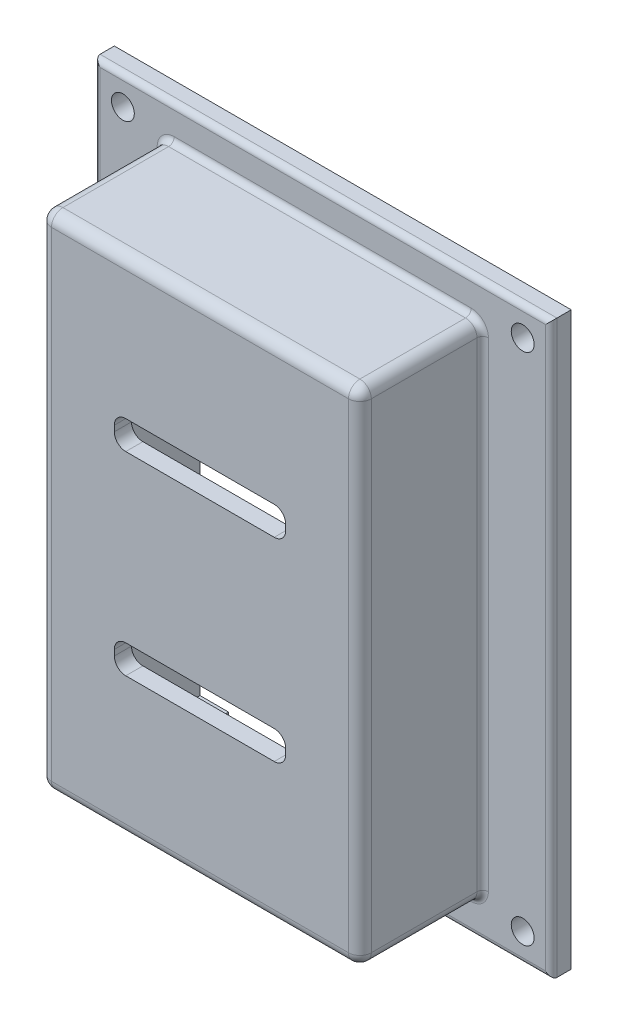
SolidWorks part; units mm, degrees
ref_plane "Front Plane" through (0, 0, 0) normal (0, 0, 1) x (1, 0, 0)
ref_plane "Top Plane" through (0, 0, 0) normal (0, 1, 0) x (1, 0, 0)
ref_plane "Right Plane" through (0, 0, 0) normal (1, 0, 0) x (0, 0, -1)
sketch "Sketch1" plane through (0, 0, 0) normal (0, 0, 1) x (1, 0, 0)
  line L1 (-40, 50) -> (40, 50)
  line L2 (-40, 50) -> (-40, -50)
  line L3 (-40, -50) -> (40, -50)
  line L4 (40, 50) -> (40, -50)
  line L5 (-40, 50) -> (40, -50) construction
  line L6 (-40, -50) -> (40, 50) construction
  point P0 (0, 0)
  dimension "D1" = 100
  dimension "D2" = 80
extrude "Boss-Extrude1" add sketch "Sketch1" along normal blind 3.5
sketch "Sketch3" plane through (0, 0, 3.5) normal (0, 0, 1) x (1, 0, 0)
  line L1 (-28, 44) -> (28, 44)
  line L2 (-28, 44) -> (-28, -44)
  line L3 (-28, -44) -> (28, -44)
  line L4 (28, 44) -> (28, -44)
  line L5 (-28, 44) -> (28, -44) construction
  line L6 (-28, -44) -> (28, 44) construction
  point P0 (0, 0)
  dimension "D1" = 56
  dimension "D2" = 88
extrude "Boss-Extrude2" add sketch "Sketch3" along normal blind 21.5
sketch "Sketch4" plane through (0, 0, 0) normal (0, 0, -1) x (-1, 0, 0)
  line L1 (-25, 41) -> (25, 41)
  line L2 (-25, 41) -> (-25, -41)
  line L3 (-25, -41) -> (25, -41)
  line L4 (25, 41) -> (25, -41)
  line L5 (-25, 41) -> (25, -41) construction
  line L6 (-25, -41) -> (25, 41) construction
  point P0 (0, 0)
  dimension "D1" = 50
  dimension "D2" = 82
extrude "Cut-Extrude4" cut sketch "Sketch4" against normal blind 16
sketch "Sketch7" plane through (0, 0, 16) normal (0, 0, -1) x (-1, 0, 0)
  line L0 (-18, 41) -> (18, 41)
  line L1 (25, 41) -> (-25, 41) construction
  line L2 (25, 41) -> (-25, 41) construction
  line L3 (18, 41) -> (18, 34)
  line L4 (18, 34) -> (25, 34)
  line L5 (25, -41) -> (25, 41) construction
  line L6 (25, 34) -> (25, -34)
  line L7 (25, -34) -> (18, -34)
  line L8 (18, -34) -> (18, -41)
  line L9 (-25, -41) -> (25, -41) construction
  line L10 (18, -41) -> (-18, -41)
  line L11 (-18, -41) -> (-18, -34)
  line L12 (-18, -34) -> (-25, -34)
  line L13 (-25, 41) -> (-25, -41) construction
  line L14 (-25, -34) -> (-25, 34)
  line L15 (-25, 34) -> (-18, 34)
  line L16 (-18, 34) -> (-18, 41)
  dimension "D1" = 68
  dimension "D2" = 7
  dimension "D3" = 36
  dimension "D4" = 7
  dimension "D5" = 68
  dimension "D6" = 36
  dimension "D7" = 7
  dimension "D8" = 7
extrude "Cut-Extrude5" cut sketch "Sketch7" against normal blind 6
sketch "Sketch8" plane through (0, 0, 25) normal (0, 0, 1) x (1, 0, 0)
  line L1 (-15, -19.5) -> (15, -19.5)
  line L2 (-15, -19.5) -> (-15, -14.5)
  line L3 (-15, -14.5) -> (15, -14.5)
  line L4 (15, -19.5) -> (15, -14.5)
  line L5 (-15, -19.5) -> (15, -14.5) construction
  line L6 (-15, -14.5) -> (15, -19.5) construction
  point P0 (0, -17)
  point P5 (0, 0)
  dimension "D1" = 5
  dimension "D2" = 17
  dimension "D3" = 30
extrude "Cut-Extrude6" cut sketch "Sketch8" against normal blind 6
mirror "Mirror1" about plane through (0, 0, 0) normal (0, 1, 0) of "Cut-Extrude6"
sketch "Sketch9" plane through (0, -50, 0) normal (0, -1, 0) x (1, 0, 0)
  line L0 (-40, 0) -> (40, 0) construction
  line L1 (-20, 0) -> (20, 0)
  line L2 (-20, 0) -> (-20, 12)
  line L3 (-20, 12) -> (20, 12)
  line L4 (20, 0) -> (20, 12)
  line L5 (-40, 3.5) -> (-40, 0) construction
  dimension "D1" = 20
  dimension "D2" = 40
  dimension "D3" = 12
extrude "Cut-Extrude7" cut sketch "Sketch9" against normal up to next
sketch "Sketch10" plane through (0, 0, 0) normal (0, 0, -1) x (-1, 0, 0)
  line L1 (-35, 45) -> (35, 45)
  line L2 (-35, 45) -> (-35, -45)
  line L3 (-35, -45) -> (35, -45)
  line L4 (35, 45) -> (35, -45)
  line L5 (-35, 45) -> (35, -45) construction
  line L6 (-35, -45) -> (35, 45) construction
  point P0 (0, 0)
  dimension "D1" = 90
  dimension "D2" = 70
hole_wizard "Ø4.0mm Dowel Hole1" positions "Sketch11" profile "Sketch12" hole size "Ø4.0" standard "ANSI Metric" end condition through all
sketch "Sketch11" plane through (0, 0, 0) normal (0, 0, -1) x (-1, 0, 0)
  point P0 (-35, 45)
  point P3 (35, 45)
  point P6 (35, -45)
  point P9 (-35, -45)
sketch "Sketch12" plane through (35, 45, 0) normal (1, 0, 0) x (0, 1, 0)
  line L0 (0, 0) -> (0, 25)
  line L1 (0, 25) -> (2, 25)
  line L2 (2, 25) -> (2, 0)
  line L5 (2, 0) -> (0, 0)
  line L11 (0, -6.35) -> (0, 107.95) construction
  dimension "Thru Hole Dia." = 4
  dimension "Thru Hole Depth" = 25
fillet "Fillet1" radius 7 4 edges at (-18, 34, 19) (18, 34, 19) (18, -34, 19) (-18, -34, 19)
fillet "Fillet2" radius 2 15 edges at (28, -44, 14.25) (-28, -44, 14.25) (-15, 19.5, 23.5) (15, 19.5, 23.5) (15, 14.5, 23.5) (-15, 14.5, 23.5) (-15, -19.5, 23.5) (-15, -14.5, 23.5) (15, -14.5, 23.5) (15, -19.5, 23.5) (-28, 0, 25) (-28, 44, 14.25) (0, 44, 25) (28, 0, 25) (28, 44, 14.25)
fillet "Fillet3" radius 1 14 edges at (23, -44, 3.5) (27.4142, -43.4142, 3.5) (28, 0, 3.5) (27.4142, 43.4142, 3.5) (0, 44, 3.5) (-27.4142, 43.4142, 3.5) (-23, -44, 3.5) (-27.4142, -43.4142, 3.5) (30, -50, 3.5) (40, 0, 3.5) (0, 50, 3.5) (-30, -50, 3.5) (-40, 0, 3.5) (-28, 0, 3.5)
fillet "Fillet4" radius 2 3 edges at (-27.4142, -43.4142, 24.4142) (27.4142, -43.4142, 24.4142) (0, -44, 25)
